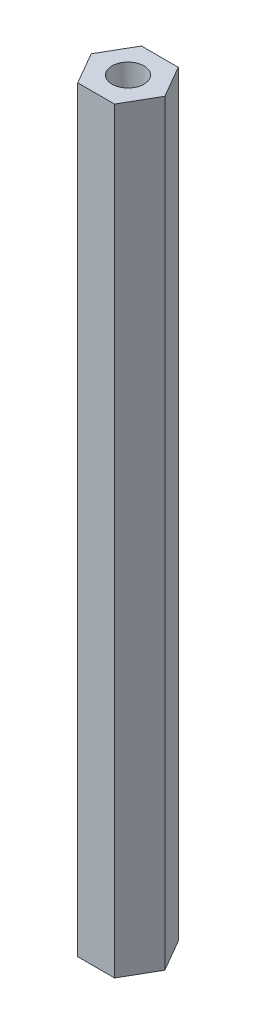
SolidWorks part; units mm, degrees
ref_plane "Front Plane" through (0, 0, 0) normal (0, 0, 1) x (1, 0, 0)
ref_plane "Top Plane" through (0, 0, 0) normal (0, 1, 0) x (1, 0, 0)
ref_plane "Right Plane" through (0, 0, 0) normal (1, 0, 0) x (0, 0, -1)
sketch "Sketch1" plane through (0, 0, 0) normal (0, 1, 0) x (1, 0, 0)
  line L1 (2.3094, 4) -> (-2.3094, 4)
  line L2 (-2.3094, 4) -> (-4.6188, 0)
  line L3 (-4.6188, 0) -> (-2.3094, -4)
  line L4 (-2.3094, -4) -> (2.3094, -4)
  line L5 (2.3094, -4) -> (4.6188, 0)
  line L6 (4.6188, 0) -> (2.3094, 4)
  circle A0 centre (0, 0) radius 4 construction
  dimension "D1" = 8
extrude "Boss-Extrude1" add sketch "Sketch1" along normal blind 47.498 and the other way blind 47.498
sketch "Sketch2" plane through (0, 47.498, 0) normal (0, 1, 0) x (1, 0, 0)
  circle A0 centre (0, 0) radius 2
  dimension "D1" = 4
sketch "Sketch3" plane through (0, -47.498, 0) normal (0, -1, 0) x (1, 0, 0)
  circle A0 centre (0, 0) radius 2
  dimension "D1" = 4
extrude "Cut-Extrude1" cut sketch "Sketch3" against normal blind 11.1
extrude "Cut-Extrude2" cut sketch "Sketch2" against normal blind 10
